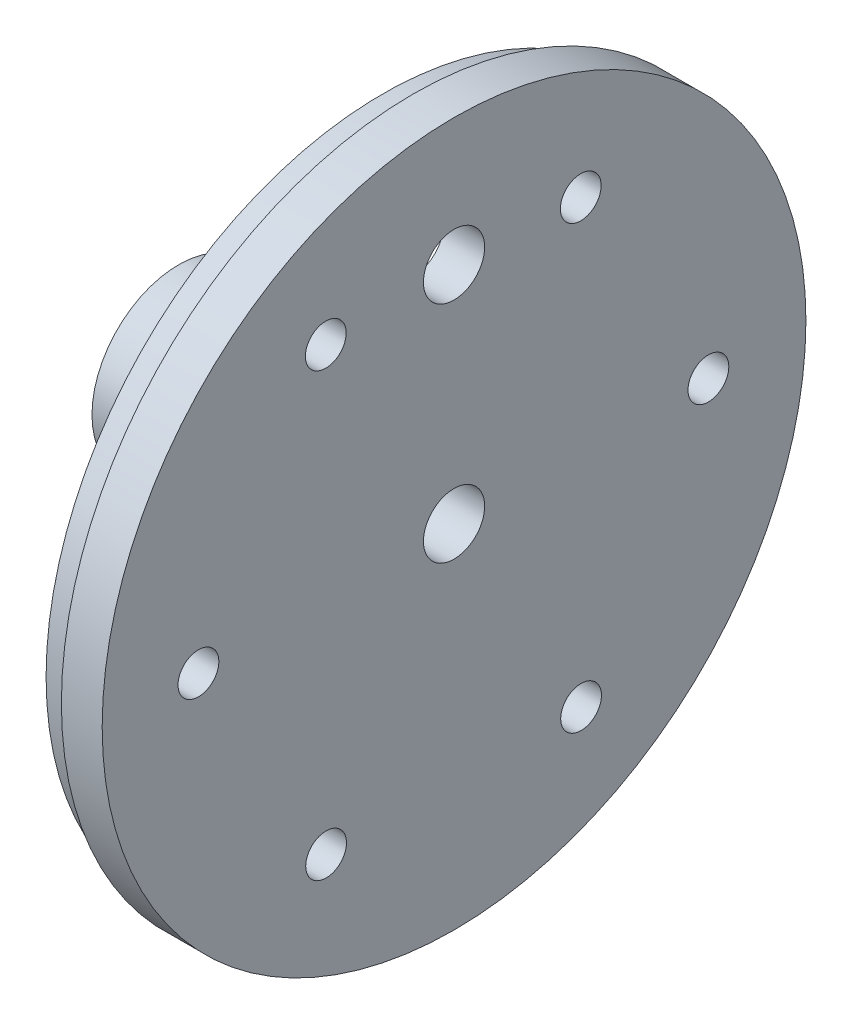
SolidWorks part; units mm, degrees
ref_plane "Front Plane" through (0, 0, 0) normal (0, 0, 1) x (1, 0, 0)
ref_plane "Top Plane" through (0, 0, 0) normal (0, 1, 0) x (1, 0, 0)
ref_plane "Right Plane" through (0, 0, 0) normal (1, 0, 0) x (0, 0, -1)
sketch "Sketch1" plane through (0, 0, 0) normal (1, 0, 0) x (0, 0, -1)
  circle A0 centre (0, 0) radius 34.5
extrude "Boss-Extrude1" add sketch "Sketch1" along normal mid plane 4
sketch "Sketch2" plane through (-2, 0, 0) normal (-1, 0, 0) x (0, 0, 1)
  circle A0 centre (0, 0) radius 8.5
  dimension "D1" = 17
extrude "Boss-Extrude2" add sketch "Sketch2" along normal blind 23
sketch "Sketch3" plane through (2, 0, 0) normal (1, 0, 0) x (0, 0, -1)
  circle A0 centre (0, 0) radius 10
sketch "Sketch4" plane through (-25, 0, 0) normal (-1, 0, 0) x (0, 0, 1)
  circle A0 centre (0, 0) radius 3
extrude "Cut-Extrude1" cut sketch "Sketch4" against normal blind 30
ref_plane "Plane1" through (0, 8.5, 0) normal (0, 1, 0) x (1, 0, 0)
sketch "Sketch5" plane through (0, 8.5, 0) normal (0, 1, 0) x (1, 0, 0)
  line L0 (-25, 8.5) -> (-25, -8.5) construction
  circle A0 centre (-19.5, 0) radius 1.5
  dimension "D1" = 5.5
extrude "Cut-Extrude2" cut sketch "Sketch5" against normal up to next
sketch "Sketch6" plane through (0, 0, 0) normal (0, 0, 1) x (1, 0, 0)
  line L0 (-25, 8.5) -> (-25, -8.5) construction
  circle A0 centre (-19.5, 0) radius 1.5
  dimension "D1" = 5.5
extrude "Cut-Extrude3" cut sketch "Sketch6" against normal up to next
sketch "Sketch19" plane through (-2, 0, 0) normal (-1, 0, 0) x (0, 0, 1)
  circle A0 centre (0, 0) radius 33
  circle A1 centre (0, 0) radius 30
  dimension "D2" = 66
  dimension "D1" = 3
extrude "Boss-Extrude5" add sketch "Sketch19" along normal blind 3
sketch "Sketch20" plane through (-2, 0, 0) normal (-1, 0, 0) x (0, 0, 1)
  circle A0 centre (-12.4224, 21.5162) radius 2
  circle A3 centre (12.5776, 21.4971) radius 2
  circle A4 centre (25.0611, -0.1631) radius 2
  circle A5 centre (12.5445, -21.8041) radius 2
  circle A6 centre (-12.4554, -21.785) radius 2
  circle A7 centre (-24.9389, -0.1249) radius 2
  point P2 (0, 0)
  point P3 (0, 0)
  point P22 (0.0611, -0.144)
  dimension "D2" = 6
sketch "Sketch21" plane through (-2, 0, 0) normal (-1, 0, 0) x (0, 0, 1)
  circle A0 centre (0, 22) radius 3
  point P2 (0, 0)
  dimension "D1" = 22
extrude "Cut-Extrude6" cut sketch "Sketch21" against normal blind 10
extrude "Cut-Extrude7" cut sketch "Sketch20" against normal blind 10
equation "\"÷6.00mm\"=6"
